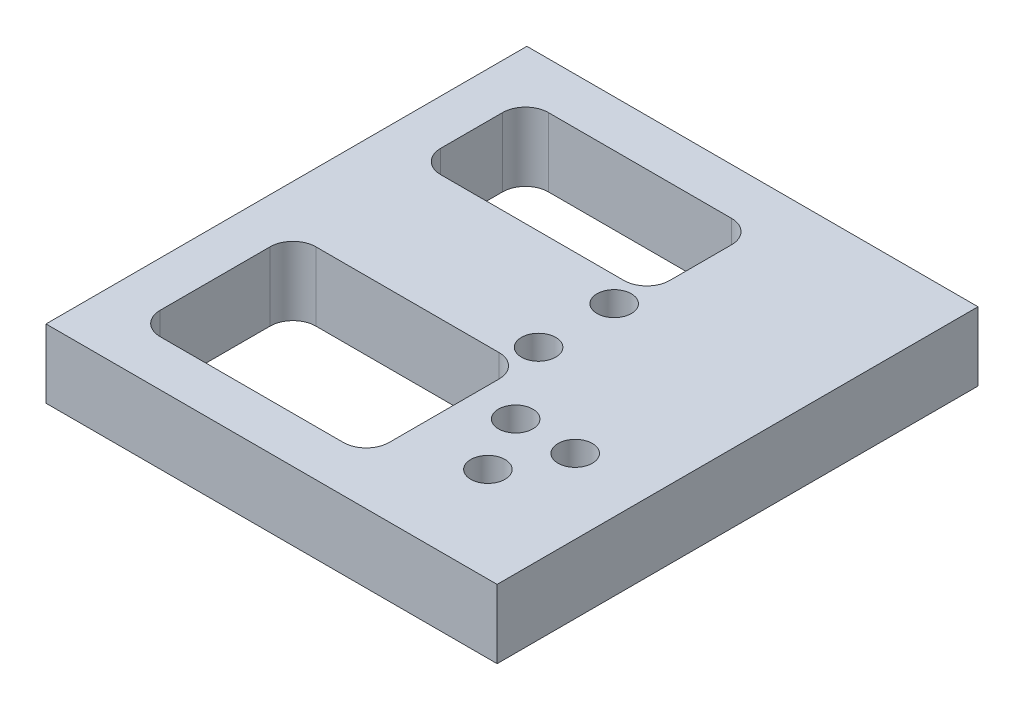
SolidWorks part; units mm, degrees
material "K110"
ref_plane "Front Plane" through (0, 0, 0) normal (0, 0, 1) x (1, 0, 0)
ref_plane "Top Plane" through (0, 0, 0) normal (0, 1, 0) x (1, 0, 0)
ref_plane "Right Plane" through (0, 0, 0) normal (1, 0, 0) x (0, 0, -1)
sketch "Sketch1" plane through (0, 0, 0) normal (0, 1, 0) x (1, 0, 0)
  line L1 (-98.5, -105) -> (98.5, -105)
  line L2 (-98.5, -105) -> (-98.5, 105)
  line L3 (-98.5, 105) -> (98.5, 105)
  line L4 (98.5, -105) -> (98.5, 105)
  line L5 (-98.5, -105) -> (98.5, 105) construction
  line L6 (-98.5, 105) -> (98.5, -105) construction
  point P0 (0, 0)
  dimension "D1" = 210
  dimension "D2" = 197
extrude "Boss-Extrude1" add sketch "Sketch1" against normal blind 30
sketch "Sketch2" plane through (0, 0, 0) normal (0, 1, 0) x (1, 0, 0)
  line L0 (-29.25, -63.53) -> (-29.25, -47.4) construction
  line L1 (-32.25, -44.4) -> (-36.25, -44.4) construction
  line L2 (-42.25, -38.4) -> (-42.25, -27.27) construction
  line L3 (-42.25, -27.27) -> (-61.37, -27.27) construction
  line L12 (-64.37, -30.27) -> (-64.37, -71.53) construction
  line L13 (-61.37, -74.53) -> (3.88, -74.53) construction
  line L14 (-17.25, -47.4) -> (-17.25, -63.53) construction
  line L15 (-10.25, -44.4) -> (-14.25, -44.4) construction
  line L16 (-4.25, -27.27) -> (-4.25, -38.4) construction
  line L17 (3.88, -27.27) -> (-4.25, -27.27) construction
  line L18 (6.88, -71.53) -> (6.88, -30.27) construction
  line L19 (-29.25, -63.53) -> (-29.25, -47.4)
  line L20 (-32.25, -44.4) -> (-36.25, -44.4)
  line L21 (-42.25, -38.4) -> (-42.25, -27.27)
  line L22 (-42.25, -27.27) -> (-61.37, -27.27)
  line L23 (-64.37, -30.27) -> (-64.37, -71.53)
  line L24 (-61.37, -74.53) -> (3.88, -74.53)
  line L25 (-17.25, -47.4) -> (-17.25, -63.53)
  line L26 (-10.25, -44.4) -> (-14.25, -44.4)
  line L27 (-4.25, -27.27) -> (-4.25, -38.4)
  line L28 (3.88, -27.27) -> (-4.25, -27.27)
  line L29 (6.88, -71.53) -> (6.88, -30.27)
  line L30 (-4.25, 47.73) -> (3.88, 47.73) construction
  line L31 (-4.25, 69.53) -> (-4.25, 47.73) construction
  line L32 (-42.25, 69.53) -> (-4.25, 69.53) construction
  line L33 (-42.25, 47.73) -> (-42.25, 69.53) construction
  line L34 (-61.37, 47.73) -> (-42.25, 47.73) construction
  line L35 (-64.37, 71.53) -> (-64.37, 50.73) construction
  line L36 (3.88, 74.53) -> (-61.37, 74.53) construction
  line L37 (6.88, 50.73) -> (6.88, 71.53) construction
  line L38 (-4.25, 47.73) -> (3.88, 47.73)
  line L39 (-4.25, 69.53) -> (-4.25, 47.73)
  line L40 (-42.25, 69.53) -> (-4.25, 69.53)
  line L41 (-42.25, 47.73) -> (-42.25, 69.53)
  line L42 (-61.37, 47.73) -> (-42.25, 47.73)
  line L43 (-64.37, 71.53) -> (-64.37, 50.73)
  line L44 (3.88, 74.53) -> (-61.37, 74.53)
  line L45 (6.88, 50.73) -> (6.88, 71.53)
  arc A0 (-29.25, -47.4) -> (-32.25, -44.4) centre (-32.25, -47.4) ccw construction
  arc A1 (-42.25, -38.4) -> (-36.25, -44.4) centre (-36.25, -38.4) ccw construction
  arc A2 (-61.37, -27.27) -> (-64.37, -30.27) centre (-61.37, -30.27) ccw construction
  arc A3 (-64.37, -71.53) -> (-61.37, -74.53) centre (-61.37, -71.53) ccw construction
  arc A4 (3.88, -74.53) -> (6.88, -71.53) centre (3.88, -71.53) ccw construction
  arc A5 (-29.25, -63.53) -> (-17.25, -63.53) centre (-23.25, -63.53) ccw construction
  arc A6 (-14.25, -44.4) -> (-17.25, -47.4) centre (-14.25, -47.4) ccw construction
  arc A7 (-10.25, -44.4) -> (-4.25, -38.4) centre (-10.25, -38.4) ccw construction
  arc A8 (6.88, -30.27) -> (3.88, -27.27) centre (3.88, -30.27) ccw construction
  arc A9 (-29.25, -47.4) -> (-32.25, -44.4) centre (-32.25, -47.4) ccw
  arc A10 (-42.25, -38.4) -> (-36.25, -44.4) centre (-36.25, -38.4) ccw
  arc A11 (-61.37, -27.27) -> (-64.37, -30.27) centre (-61.37, -30.27) ccw
  arc A12 (-64.37, -71.53) -> (-61.37, -74.53) centre (-61.37, -71.53) ccw
  arc A13 (3.88, -74.53) -> (6.88, -71.53) centre (3.88, -71.53) ccw
  arc A14 (-29.25, -63.53) -> (-17.25, -63.53) centre (-23.25, -63.53) ccw
  arc A15 (-14.25, -44.4) -> (-17.25, -47.4) centre (-14.25, -47.4) ccw
  arc A16 (-10.25, -44.4) -> (-4.25, -38.4) centre (-10.25, -38.4) ccw
  arc A17 (6.88, -30.27) -> (3.88, -27.27) centre (3.88, -30.27) ccw
  circle A18 centre (53, -63.53) radius 2.5 construction
  circle A19 centre (66, -38.4) radius 2.5 construction
  circle A20 centre (40, -38.4) radius 2.5 construction
  circle A21 centre (17.88, -6.27) radius 2.5 construction
  circle A22 centre (17.88, 26.73) radius 2.5 construction
  arc A23 (3.88, 47.73) -> (6.88, 50.73) centre (3.88, 50.73) ccw construction
  arc A24 (-64.37, 50.73) -> (-61.37, 47.73) centre (-61.37, 50.73) ccw construction
  arc A25 (-61.37, 74.53) -> (-64.37, 71.53) centre (-61.37, 71.53) ccw construction
  arc A26 (6.88, 71.53) -> (3.88, 74.53) centre (3.88, 71.53) ccw construction
  circle A27 centre (53, -63.53) radius 2.5
  circle A28 centre (66, -38.4) radius 2.5
  circle A29 centre (40, -38.4) radius 2.5
  circle A30 centre (17.88, -6.27) radius 2.5
  circle A31 centre (17.88, 26.73) radius 2.5
  arc A32 (3.88, 47.73) -> (6.88, 50.73) centre (3.88, 50.73) ccw
  arc A33 (-64.37, 50.73) -> (-61.37, 47.73) centre (-61.37, 50.73) ccw
  arc A34 (-61.37, 74.53) -> (-64.37, 71.53) centre (-61.37, 71.53) ccw
  arc A35 (6.88, 71.53) -> (3.88, 74.53) centre (3.88, 71.53) ccw
sketch "Sketch3" plane through (0, 0, 0) normal (0, 1, 0) x (1, 0, 0)
  line L1 (-68.745, 84.63) -> (11.255, 84.63)
  line L2 (-78.745, 74.63) -> (-78.745, 47.63)
  line L3 (-68.745, 37.63) -> (11.255, 37.63)
  line L4 (21.255, 74.63) -> (21.255, 47.63)
  line L8 (-64.37, -50.9) -> (6.88, -50.9) construction
  line L9 (-68.745, -16.9) -> (11.255, -16.9)
  line L10 (-78.745, -26.9) -> (-78.745, -74.9)
  line L11 (-68.745, -84.9) -> (11.255, -84.9)
  line L12 (21.255, -26.9) -> (21.255, -74.9)
  line L13 (-64.37, -30.27) -> (-64.37, -71.53) construction
  line L14 (6.88, -71.53) -> (6.88, -30.27) construction
  line L15 (-28.745, -74.53) -> (-28.745, -16.9) construction
  line L16 (-61.37, -74.53) -> (3.88, -74.53) construction
  line L17 (-28.745, 84.63) -> (-28.745, 47.73) construction
  line L18 (-64.37, 61.13) -> (6.88, 61.13) construction
  line L19 (-64.37, 71.53) -> (-64.37, 50.73) construction
  line L20 (6.88, 50.73) -> (6.88, 71.53) construction
  arc A0 (-78.745, 47.63) -> (-68.745, 37.63) centre (-68.745, 47.63) ccw
  arc A1 (11.255, 37.63) -> (21.255, 47.63) centre (11.255, 47.63) ccw
  arc A2 (21.255, 74.63) -> (11.255, 84.63) centre (11.255, 74.63) ccw
  arc A3 (-68.745, 84.63) -> (-78.745, 74.63) centre (-68.745, 74.63) ccw
  circle A4 centre (17.88, 26.73) radius 7.5
  circle A5 centre (17.88, -6.27) radius 7.5
  circle A6 centre (53, -63.53) radius 7.5
  circle A7 centre (66, -38.4) radius 7.5
  circle A8 centre (40, -38.4) radius 7.5
  arc A9 (-78.745, -74.9) -> (-68.745, -84.9) centre (-68.745, -74.9) ccw
  arc A10 (11.255, -84.9) -> (21.255, -74.9) centre (11.255, -74.9) ccw
  arc A11 (21.255, -26.9) -> (11.255, -16.9) centre (11.255, -26.9) ccw
  arc A12 (-68.745, -16.9) -> (-78.745, -26.9) centre (-68.745, -26.9) ccw
  dimension "D5" = 10
  dimension "D6" = 15
  dimension "D11" = 10
  dimension "D2" = 100
  dimension "D3" = 47
  dimension "D7" = 68
  dimension "D8" = 100
extrude "Cut-Extrude2" cut sketch "Sketch3" against normal up to next
sketch "Sketch4" plane through (0, -30, 0) normal (0, -1, 0) x (1, 0, 0)
  circle A0 centre (17.88, -26.73) radius 9
  circle A1 centre (17.88, 6.27) radius 9
  circle A2 centre (40, 38.4) radius 9
  circle A3 centre (66, 38.4) radius 9
  circle A4 centre (53, 63.53) radius 9
  dimension "D1" = 18
extrude "Cut-Extrude3" cut sketch "Sketch4" against normal blind 5
